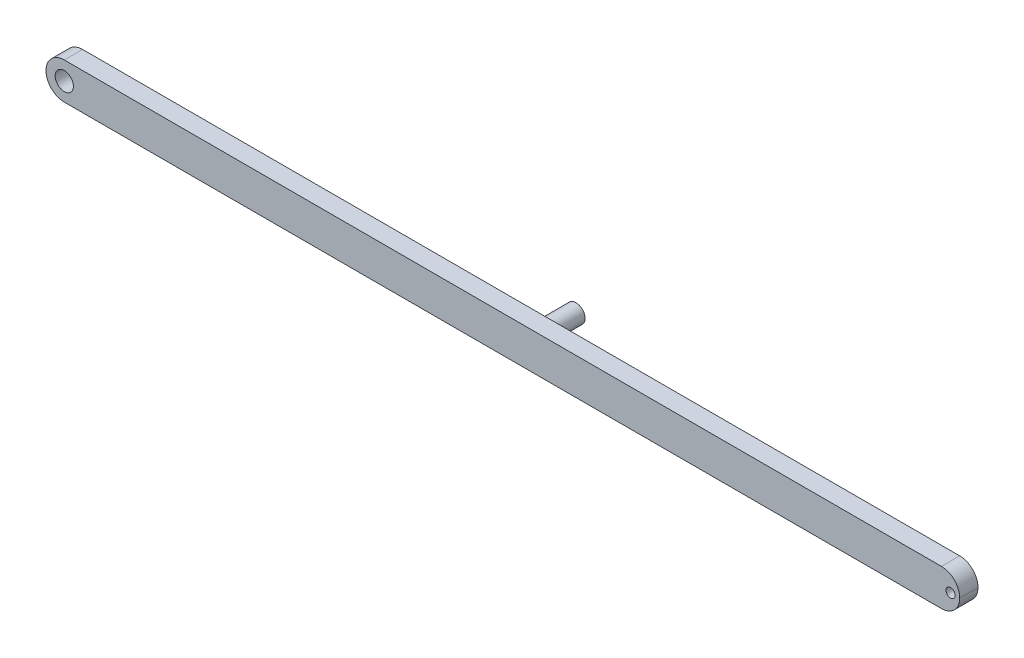
SolidWorks part; units mm, degrees
ref_plane "Front Plane" through (0, 0, 0) normal (0, 0, 1) x (1, 0, 0)
ref_plane "Top Plane" through (0, 0, 0) normal (0, 1, 0) x (1, 0, 0)
ref_plane "Right Plane" through (0, 0, 0) normal (1, 0, 0) x (0, 0, -1)
sketch "Sketch1" plane through (0, 0, 0) normal (0, 0, 1) x (1, 0, 0)
  line L1 (-250, 10) -> (250, 10)
  line L2 (-250, 10) -> (-250, -10)
  line L3 (-250, -10) -> (250, -10)
  line L4 (250, 10) -> (250, -10)
  line L5 (-250, 10) -> (250, -10) construction
  line L6 (-250, -10) -> (250, 10) construction
  circle A0 centre (-240, 0) radius 5
  circle A1 centre (245, 0) radius 2.5
  point P0 (0, 0)
  dimension "D4" = 5
  dimension "D5" = 10
  dimension "D6" = 5
  dimension "D1" = 500
  dimension "D2" = 20
  dimension "D3" = 10
extrude "Boss-Extrude1" add sketch "Sketch1" along normal blind 10
fillet "Fillet1" radius 10 4 edges at (250, -10, 5) (250, 10, 5) (-250, -10, 5) (-250, 10, 5)
sketch "Sketch2" plane through (0, 0, 0) normal (0, 0, -1) x (-1, 0, 0)
  circle A0 centre (-10, 0) radius 5
  dimension "D1" = 10
  dimension "D2" = 10
extrude "Boss-Extrude2" add sketch "Sketch2" along normal blind 20
fillet "Fillet2" radius 5 1 edges at (15, 0, 0)
